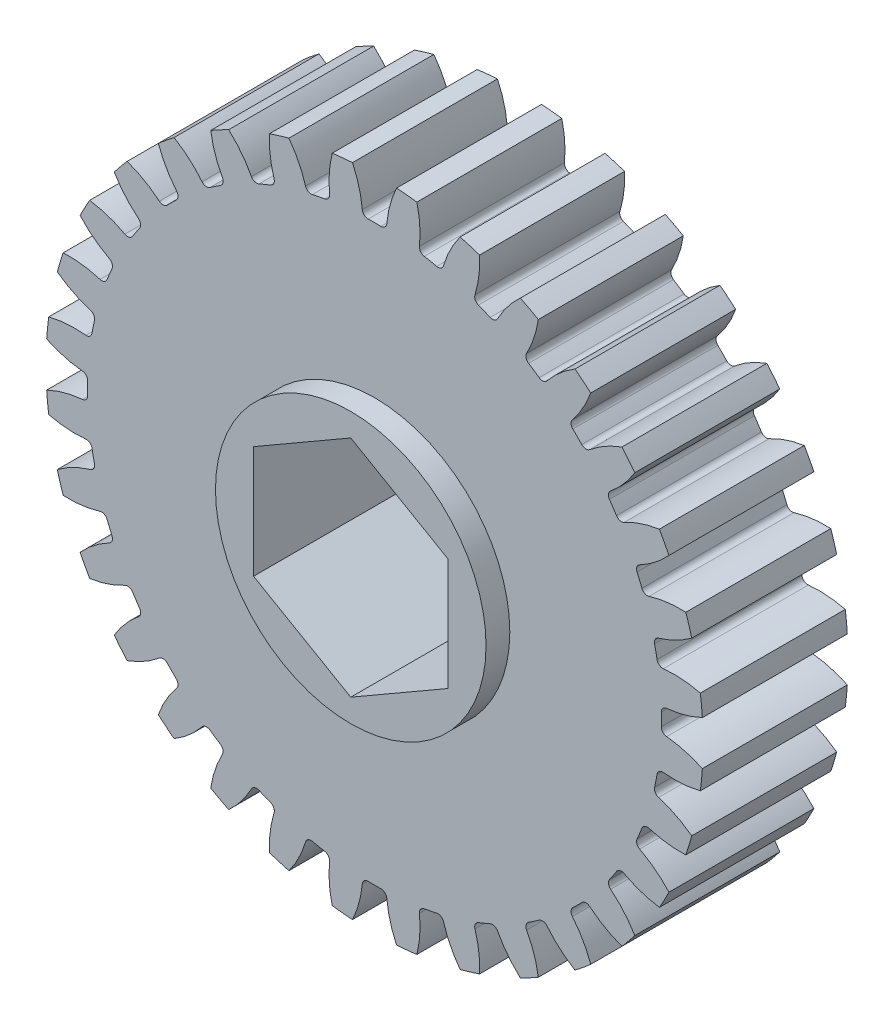
SolidWorks part; units mm, degrees
material "7075-T6 (SN)"
ref_plane "Alzado" through (0, 0, 0) normal (0, 0, 1) x (1, 0, 0)
ref_plane "Planta" through (0, 0, 0) normal (0, 1, 0) x (1, 0, 0)
ref_plane "Vista lateral" through (0, 0, 0) normal (1, 0, 0) x (0, 0, -1)
sketch "Croquis1" plane through (0, 0, 0) normal (0, 0, 1) x (1, 0, 0)
  circle A0 centre (0, 0) radius 20.32 construction
  circle A1 centre (0, 0) radius 21.59
  dimension "D" = 40.64
  dimension "OD" = 43.18
extrude "Saliente-Extruir1" add sketch "Croquis1" along normal mid plane 9.525
sketch "Croquis2" plane through (0, 0, 0) normal (0, 0, 1) x (1, 0, 0)
  line L0 (0, 0) -> (0, 21.59) construction
  line L1 (0, 0) -> (4.212, 21.1752) construction
  line L2 (0, 0) -> (2.1162, 21.486) construction
  line L3 (-0.7804, 18.8345) -> (0, 0) construction
  line L4 (-0.9971, 20.2955) -> (0.9971, 20.2955) construction
  line L5 (0.9971, 20.2955) -> (2.9816, 20.1001) construction
  line L6 (-1.3214, 21.5495) -> (0, 16.4402) construction
  circle A0 centre (0, 0) radius 21.59 construction
  arc A2 (0.7804, 18.8345) -> (-0.7804, 18.8345) centre (0, 0) ccw
  circle A5 centre (0, 0) radius 20.32 construction
  arc A6 (-1.449, 21.5413) -> (-0.7804, 18.8345) centre (-7.7657, 18.545) cw
  arc A7 (1.449, 21.5413) -> (0.7804, 18.8345) centre (7.7657, 18.545) ccw
  arc A8 (1.449, 21.5413) -> (-1.449, 21.5413) centre (0, 0) ccw
  dimension "D1" = 11.25
  dimension "D2" = 5.625
  dimension "B" = 1.4694
  dimension "Pressure Angle" = 14.5
extrude "Cortar-Extruir1" cut sketch "Croquis2" against normal through all both and the other way through all
fillet "Redondeo1" radius 0.381 2 edges at (0.7804, 18.8345, 0) (-0.7804, 18.8345, 0)
pattern_circular "MatrizC1" count 32 over 360 about axis through (0, 0, 4.7625) along (0, 0, -1) of "Cortar-Extruir1", "Redondeo1"
sketch "Croquis3" plane through (0, 0, 0) normal (0, 0, 1) x (1, 0, 0)
  circle A0 centre (0, 0) radius 8.89
  dimension "sp" = 17.78
extrude "Saliente-Extruir2" add sketch "Croquis3" along normal mid plane 12.6492
sketch "Croquis4" plane through (0, 0, 0) normal (0, 0, 1) x (1, 0, 0)
  line L0 (6.3881, 3.6882) -> (0, 7.3763)
  line L1 (0, 7.3323) -> (-6.35, 3.6662)
  line L2 (-6.35, 3.6662) -> (-6.35, -3.6662)
  line L3 (-6.35, -3.6662) -> (0, -7.3323)
  line L4 (0, -7.3323) -> (6.35, -3.6662)
  line L5 (6.35, -3.6662) -> (6.35, 3.6662)
  line L6 (6.35, 3.6662) -> (0, 7.3323)
  line L7 (0, 7.3763) -> (-6.3881, 3.6882)
  line L8 (-6.3881, 3.6882) -> (-6.3881, -3.6882)
  line L9 (-6.3881, -3.6882) -> (0, -7.3763)
  line L10 (0, -7.3763) -> (6.3881, -3.6882)
  line L11 (6.3881, -3.6882) -> (6.3881, 3.6882)
  circle A0 centre (0, 0) radius 6.35 construction
  dimension "D1" = 12.7
  dimension "D2" = 0.0381
extrude "Cortar-Extruir2" cut sketch "Croquis4" against normal through all both and the other way through all contours L7 L8 L9 L10 L11 L0
sketch "Croquis5" [suppressed] plane through (0, 0, 0) normal (0, 0, 1) x (1, 0, 0)
  circle A1 centre (0, 0) radius 21.8948
  circle A3 centre (0, 0) radius 26.67 construction
  circle A4 centre (0, 0) radius 8.89 construction
  circle A5 centre (0, 0) radius 8.89
  dimension "D1" = 4.7752
extrude "Cortar-Extruir3" [suppressed] cut sketch "Croquis5" along normal through all from offset 1.143
fillet "Redondeo2" [suppressed] radius 3.175
mirror "Simetría1" [suppressed] about plane through (0, 0, 0) normal (0, 0, 1)
other "PropertyManager" [suppressed]
equation "\"Number of teeth\"= 32"
equation "\"Diametral Pitch\"= 20"
equation "\"Pressure Angle\"= 14.5"
equation "\"D@Croquis1\"=\"Number of teeth\"/\"Diametral Pitch\""
equation "\"OD@Croquis1\"=(\"Number of teeth\"+2) /\"Diametral Pitch\""
equation "\"D2@Croquis2\"=(360 / \"Number of teeth\")/ 2."
equation "\"D1@Croquis2\"=360 / \"Number of teeth\""
equation "\"B@Croquis2\"=1.157 / \"Diametral Pitch\""
equation "\"Pressure Angle@Croquis2\" = \"Pressure Angle\""
equation "\"D1@Redondeo1\"=(pi / \"Diametral Pitch\") * .0955"
equation "\"D1@MatrizC1\"=\"Number of teeth\""
equation "\"Tt@Saliente-Extruir1\"=if( \"Number of teeth\"=>30,0.375,0.475)"
